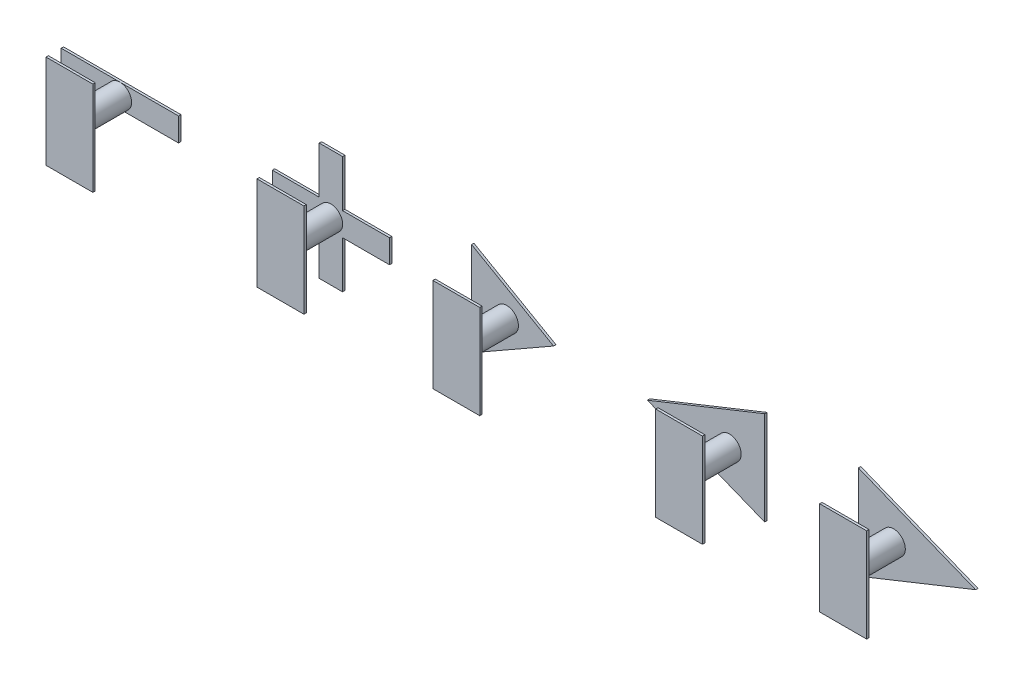
SolidWorks part; units mm, degrees
ref_plane "Front Plane" through (0, 0, 0) normal (0, 0, 1) x (1, 0, 0)
ref_plane "Top Plane" through (0, 0, 0) normal (0, 1, 0) x (1, 0, 0)
ref_plane "Right Plane" through (0, 0, 0) normal (1, 0, 0) x (0, 0, -1)
sketch "Sketch1" plane through (0, 0, 0) normal (0, 0, 1) x (1, 0, 0)
  line L1 (-61, 40) -> (61, 40)
  line L2 (-63, 38) -> (-63, -38)
  line L3 (-61, -40) -> (61, -40)
  line L4 (63, 38) -> (63, -38)
  line L5 (-63, 40) -> (63, -40) construction
  line L6 (-63, -40) -> (63, 40) construction
  arc A0 (61, 40) -> (63, 38) centre (61, 38) cw
  arc A1 (63, -38) -> (61, -40) centre (61, -38) cw
  arc A2 (-61, -40) -> (-63, -38) centre (-61, -38) cw
  arc A3 (-63, 38) -> (-61, 40) centre (-61, 38) cw
  point P0 (0, 0)
  dimension "D1" = 2
sketch "Sketch2" plane through (0, 0, 0) normal (0, 0, 1) x (1, 0, 0)
  line L0 (-5, 5.1169) -> (-5, -5.1169)
  line L1 (-4.2428, -5.5457) -> (4.2854, -0.4287)
  line L2 (4.2854, 0.4287) -> (-4.2428, 5.5457)
  line L3 (-10, -1.5) -> (-10, 1.5)
  line L4 (-10.5, 2) -> (-14, 2)
  line L5 (-14, 2) -> (-14, 5.5)
  line L6 (-14.5, 6) -> (-17.5, 6)
  line L7 (-18, 5.5) -> (-18, 2)
  line L8 (-18, 2) -> (-21.5, 2)
  line L9 (-22, 1.5) -> (-22, -1.5)
  line L10 (-21.5, -2) -> (-18, -2)
  line L11 (-18, -2) -> (-18, -5.5)
  line L12 (-17.5, -6) -> (-14.5, -6)
  line L13 (-14, -5.5) -> (-14, -2)
  line L14 (-14, -2) -> (-10.5, -2)
  line L15 (-28, 1.5) -> (-28, -1.5)
  line L16 (-28.5, -2) -> (-39.5, -2)
  line L17 (-40, -1.5) -> (-40, 1.5)
  line L18 (-39.5, 2) -> (-28.5, 2)
  line L19 (10, 4.5) -> (10, -4.5)
  line L20 (10.5, -5) -> (12.5, -5)
  line L21 (13, -4.5) -> (13, -2)
  line L22 (12.5, 5) -> (10.5, 5)
  line L23 (28, 5.2306) -> (28, -5.2306)
  line L24 (21.2969, 5.6875) -> (13, 2)
  line L25 (13, -2) -> (21.2969, -5.6875)
  line L26 (22, -5.2306) -> (22, 5.2306)
  line L27 (13, 2) -> (13, 4.5)
  line L28 (28.7031, -5.6875) -> (37, -2)
  line L29 (28.7031, 5.6875) -> (37, 2)
  line L30 (37, 2) -> (37, 4.5)
  line L31 (37.5, 5) -> (39.5, 5)
  line L32 (40, 4.5) -> (40, -4.5)
  line L33 (39.5, -5) -> (37.5, -5)
  line L34 (37, -4.5) -> (37, -2)
  arc A0 (-39.5, -2) -> (-40, -1.5) centre (-39.5, -1.5) cw
  arc A1 (-40, 1.5) -> (-39.5, 2) centre (-39.5, 1.5) cw
  arc A2 (-28.5, 2) -> (-28, 1.5) centre (-28.5, 1.5) cw
  arc A3 (-28, -1.5) -> (-28.5, -2) centre (-28.5, -1.5) cw
  arc A4 (-14.5, -6) -> (-14, -5.5) centre (-14.5, -5.5) ccw
  arc A5 (-17.5, -6) -> (-18, -5.5) centre (-17.5, -5.5) cw
  arc A6 (-21.5, -2) -> (-22, -1.5) centre (-21.5, -1.5) cw
  arc A7 (-22, 1.5) -> (-21.5, 2) centre (-21.5, 1.5) cw
  arc A8 (-18, 5.5) -> (-17.5, 6) centre (-17.5, 5.5) cw
  arc A9 (-14.5, 6) -> (-14, 5.5) centre (-14.5, 5.5) cw
  arc A10 (-10.5, 2) -> (-10, 1.5) centre (-10.5, 1.5) cw
  arc A11 (-10.5, -2) -> (-10, -1.5) centre (-10.5, -1.5) ccw
  arc A12 (-4.2428, -5.5457) -> (-5, -5.1169) centre (-4.5, -5.1169) cw
  arc A13 (-5, 5.1169) -> (-4.2428, 5.5457) centre (-4.5, 5.1169) cw
  arc A14 (4.2854, -0.4287) -> (4.2854, 0.4287) centre (4.0282, 0) ccw
  arc A15 (21.2969, 5.6875) -> (22, 5.2306) centre (21.5, 5.2306) cw
  arc A16 (22, -5.2306) -> (21.2969, -5.6875) centre (21.5, -5.2306) cw
  arc A17 (12.5, -5) -> (13, -4.5) centre (12.5, -4.5) ccw
  arc A18 (10.5, -5) -> (10, -4.5) centre (10.5, -4.5) cw
  arc A19 (10, 4.5) -> (10.5, 5) centre (10.5, 4.5) cw
  arc A20 (12.5, 5) -> (13, 4.5) centre (12.5, 4.5) cw
  arc A21 (28.7031, -5.6875) -> (28, -5.2306) centre (28.5, -5.2306) cw
  arc A22 (28, 5.2306) -> (28.7031, 5.6875) centre (28.5, 5.2306) cw
  arc A23 (37.5, -5) -> (37, -4.5) centre (37.5, -4.5) cw
  arc A24 (39.5, -5) -> (40, -4.5) centre (39.5, -4.5) ccw
  arc A25 (37, 4.5) -> (37.5, 5) centre (37.5, 4.5) cw
  arc A26 (40, 4.5) -> (39.5, 5) centre (39.5, 4.5) ccw
  dimension "D1" = 0.5
sketch "Sketch5" plane through (0, 0, 0) normal (0, 0, 1) x (1, 0, 0)
  line L0 (-21, 1) -> (-17, 1)
  line L1 (-39, 1) -> (-29, 1)
  line L2 (-39, 1) -> (-39, -1)
  line L3 (-39, -1) -> (-29, -1)
  line L4 (-29, 1) -> (-29, -1)
  line L5 (-17, 1) -> (-17, 5)
  line L6 (-17, 5) -> (-15, 5)
  line L7 (-15, 5) -> (-15, 1)
  line L8 (-15, 1) -> (-11, 1)
  line L9 (-11, 1) -> (-11, -1)
  line L10 (-11, -1) -> (-15, -1)
  line L11 (-15, -1) -> (-15, -5)
  line L12 (-15, -5) -> (-17, -5)
  line L13 (-17, -5) -> (-17, -1)
  line L14 (-17, -1) -> (-21, -1)
  line L15 (-21, -1) -> (-21, 1)
  line L16 (-4, 4) -> (-4, -4)
  line L17 (-4, -4) -> (3, 0)
  line L18 (3, 0) -> (-4, 4)
  line L19 (29, 4) -> (29, -4)
  line L20 (29, -4) -> (39, 0)
  line L21 (39, 0) -> (29, 4)
  line L22 (11, 0) -> (21, -4)
  line L23 (21, -4) -> (21, 4)
  line L24 (21, 4) -> (11, 0)
ref_plane "Plane2" through (0, 0, 0.5) normal (0, 0, 1) x (1, 0, 0)
sketch "Sketch8" plane through (0, 0, 0.5) normal (0, 0, 1) x (1, 0, 0)
  line L0 (-21, 1) -> (-17, 1)
  line L1 (-39, 1) -> (-29, 1)
  line L2 (-39, 1) -> (-39, -1)
  line L3 (-39, -1) -> (-29, -1)
  line L4 (-29, 1) -> (-29, -1)
  line L5 (-17, 1) -> (-17, 5)
  line L6 (-17, 5) -> (-15, 5)
  line L7 (-15, 5) -> (-15, 1)
  line L8 (-15, 1) -> (-11, 1)
  line L9 (-11, 1) -> (-11, -1)
  line L10 (-11, -1) -> (-15, -1)
  line L11 (-15, -1) -> (-15, -5)
  line L12 (-15, -5) -> (-17, -5)
  line L13 (-17, -5) -> (-17, -1)
  line L14 (-17, -1) -> (-21, -1)
  line L15 (-21, -1) -> (-21, 1)
  line L16 (-4, 4) -> (-4, -4)
  line L17 (-4, -4) -> (3, 0)
  line L18 (3, 0) -> (-4, 4)
  line L19 (29, 4) -> (29, -4)
  line L20 (29, -4) -> (39, 0)
  line L21 (39, 0) -> (29, 4)
  line L22 (11, 0) -> (21, -4)
  line L23 (21, -4) -> (21, 4)
  line L24 (21, 4) -> (11, 0)
ref_plane "Plane3" through (0, 0, 5) normal (0, 0, 1) x (1, 0, 0)
sketch "Sketch9" plane through (0, 0, 5) normal (0, 0, 1) x (1, 0, 0)
  circle A0 centre (-34, 0) radius 1
  circle A1 centre (-16, 0) radius 1
  circle A2 centre (-1, 0) radius 1
  circle A3 centre (18, 0) radius 1
  circle A4 centre (32, 0) radius 1
sketch "Sketch10" plane through (0, 0, 5) normal (0, 0, 1) x (1, 0, 0)
  circle A0 centre (-34, 0) radius 1
  circle A1 centre (-16, 0) radius 1
  circle A2 centre (-1, 0) radius 1
  circle A3 centre (18, 0) radius 1
  circle A4 centre (32, 0) radius 1
sketch "Sketch11" plane through (0, 0, 5) normal (0, 0, 1) x (1, 0, 0)
  line L1 (-36, 4) -> (-32, 4)
  line L2 (-36, 4) -> (-36, -4)
  line L3 (-36, -4) -> (-32, -4)
  line L4 (-32, 4) -> (-32, -4)
  line L5 (-18, 4) -> (-14, 4)
  line L6 (-18, 4) -> (-18, -4)
  line L7 (-18, -4) -> (-14, -4)
  line L8 (-14, 4) -> (-14, -4)
  line L9 (-3, 4) -> (1, 4)
  line L10 (-3, 4) -> (-3, -4)
  line L11 (-3, -4) -> (1, -4)
  line L12 (1, 4) -> (1, -4)
  line L13 (16, 4) -> (20, 4)
  line L14 (16, 4) -> (16, -4)
  line L15 (16, -4) -> (20, -4)
  line L16 (20, 4) -> (20, -4)
  line L17 (30, 4) -> (34, 4)
  line L18 (30, 4) -> (30, -4)
  line L19 (30, -4) -> (34, -4)
  line L20 (34, 4) -> (34, -4)
sketch "Sketch12" plane through (0, 0, 5) normal (0, 0, 1) x (1, 0, 0)
  circle A0 centre (-45, 0) radius 1.25
  circle A1 centre (45, 0) radius 1.25
  circle A2 centre (0, 10) radius 1.25
  circle A3 centre (0, -10) radius 1.25
sketch "Sketch13" plane through (0, 0, 5) normal (0, 0, 1) x (1, 0, 0)
  circle A0 centre (60, 37) radius 1
  circle A1 centre (60, -37) radius 1
  circle A2 centre (-60, -37) radius 1
  circle A3 centre (-60, 37) radius 1
  circle A4 centre (0, 37) radius 1
  circle A5 centre (0, -37) radius 1
  circle A6 centre (-60, 0) radius 1
  circle A7 centre (60, 0) radius 1
sketch "Sketch14" plane through (0, 0, 0.5) normal (0, 0, 1) x (1, 0, 0)
  line L0 (-21, 1) -> (-17, 1)
  line L1 (-39, 1) -> (-29, 1)
  line L2 (-39, 1) -> (-39, -1)
  line L3 (-39, -1) -> (-29, -1)
  line L4 (-29, 1) -> (-29, -1)
  line L5 (-17, 1) -> (-17, 5)
  line L6 (-17, 5) -> (-15, 5)
  line L7 (-15, 5) -> (-15, 1)
  line L8 (-15, 1) -> (-11, 1)
  line L9 (-11, 1) -> (-11, -1)
  line L10 (-11, -1) -> (-15, -1)
  line L11 (-15, -1) -> (-15, -5)
  line L12 (-15, -5) -> (-17, -5)
  line L13 (-17, -5) -> (-17, -1)
  line L14 (-17, -1) -> (-21, -1)
  line L15 (-21, -1) -> (-21, 1)
  line L16 (-4, 4) -> (-4, -4)
  line L17 (-4, -4) -> (3, 0)
  line L18 (3, 0) -> (-4, 4)
  line L19 (29, 4) -> (29, -4)
  line L20 (29, -4) -> (39, 0)
  line L21 (39, 0) -> (29, 4)
  line L22 (11, 0) -> (21, -4)
  line L23 (21, -4) -> (21, 4)
  line L24 (21, 4) -> (11, 0)
extrude "Boss-Extrude1" add sketch "Sketch8" along normal blind 0.2
extrude "Boss-Extrude2" add sketch "Sketch10" against normal blind 4.5 separate body
extrude "Boss-Extrude3" add sketch "Sketch11" against normal blind 0.2
